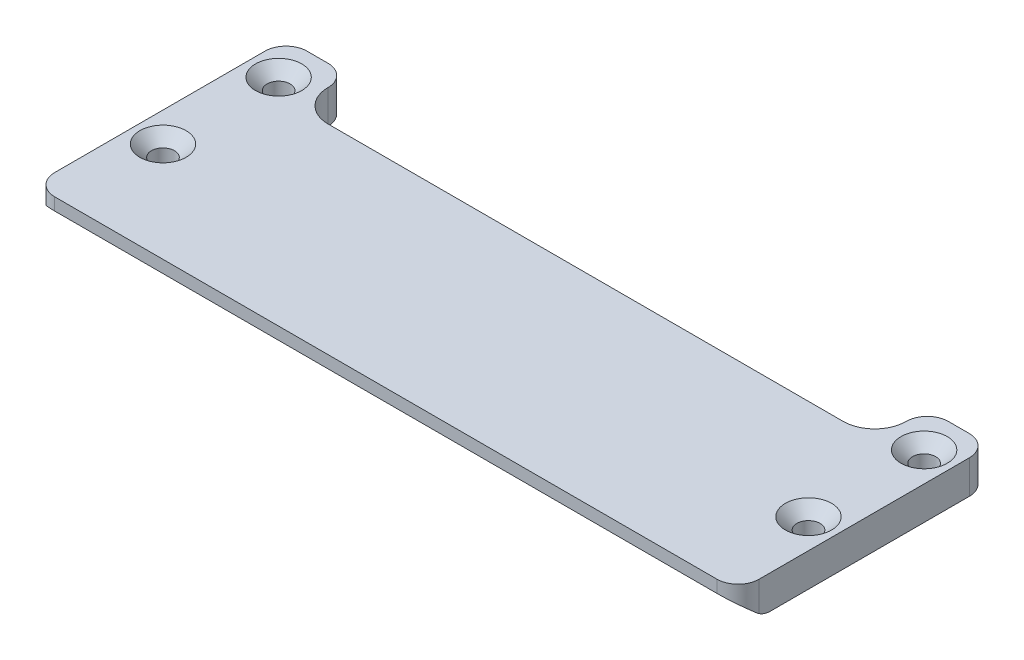
SolidWorks part; units mm, degrees
ref_plane "Front Plane" through (0, 0, 0) normal (0, 0, 1) x (1, 0, 0)
ref_plane "Top Plane" through (0, 0, 0) normal (0, 1, 0) x (1, 0, 0)
ref_plane "Right Plane" through (0, 0, 0) normal (1, 0, 0) x (0, 0, -1)
sketch "Sketch1" plane through (0, 0, 0) normal (0, 1, 0) x (1, 0, 0)
  line L1 (-33.5, -12) -> (33.5, -12)
  line L2 (-33.5, -12) -> (-33.5, 12)
  line L3 (-33.5, 12) -> (33.5, 12)
  line L4 (33.5, -12) -> (33.5, 12)
  line L5 (-33.5, -12) -> (33.5, 12) construction
  line L6 (-33.5, 12) -> (33.5, -12) construction
  point P0 (0, 0)
  dimension "D1" = 67
  dimension "D2" = 24
extrude "Boss-Extrude1" add sketch "Sketch1" along normal blind 3.175
hole_wizard "CSK for M2 Flat Head Machine Screw1" positions "Sketch2" profile "Sketch3" countersink size "M2" standard "ANSI Metric" end condition through all
sketch "Sketch2" plane through (0, 3.175, 0) normal (0, 1, 0) x (1, 0, 0)
  line L1 (-30.7, 8.5) -> (30.7, 8.5) construction
  line L2 (-30.7, 8.5) -> (-30.7, -2.5) construction
  line L4 (30.7, 8.5) -> (30.7, -2.5) construction
  line L6 (0, 0) -> (0, 8.5) construction
  line L7 (33.5, -12) -> (33.5, 12) construction
  line L8 (33.5, 12) -> (-33.5, 12) construction
  point P0 (-30.7, 8.5)
  point P2 (-30.7, -2.5)
  point P4 (30.7, -2.5)
  point P6 (30.7, 8.5)
  dimension "D1" = 2.8
  dimension "D2" = 3.5
  dimension "D3" = 11
sketch "Sketch3" plane through (-30.7, 3.175, -8.5) normal (1, 0, 0) x (0, 0, 1)
  line L0 (0, 0) -> (0, 3.175)
  line L1 (0, 3.175) -> (1.1, 3.175)
  line L2 (1.1, 3.175) -> (1.1, 1.1)
  line L3 (1.1, 1.1) -> (2.2, 0)
  line L5 (2.2, 0) -> (0, 0)
  line L6 (-1.1, 1.1) -> (-2.2, 0) construction
  line L11 (0, -6.35) -> (0, 107.95) construction
  dimension "Thru Hole Dia." = 2.2
  dimension "Thru Hole Depth" = 3.175
  dimension "Near C'Sink Dia." = 4.4
  dimension "Near C'Sink Angle" = 90
chamfer "Chamfer1" distance 2 angle 50 1 edges at (0, 0, 12) first distance on face at (0, 1.5875, 12)
sketch "Sketch4" plane through (0, 3.175, 0) normal (0, 1, 0) x (1, 0, 0)
  line L0 (33.5, 12) -> (-33.5, 12) construction
  line L1 (-27.5, 7) -> (27.5, 7)
  line L2 (-27.5, 7) -> (-27.5, 17)
  line L3 (-27.5, 17) -> (27.5, 17)
  line L4 (27.5, 7) -> (27.5, 17)
  line L5 (-27.5, 7) -> (27.5, 17) construction
  line L6 (-27.5, 17) -> (27.5, 7) construction
  line L7 (33.5, -12) -> (33.5, 12) construction
  point P0 (0, 12)
  dimension "D1" = 6
  dimension "D2" = 10
extrude "Cut-Extrude1" cut sketch "Sketch4" against normal through all
fillet "Fillet2" radius 2 1 edges at (0, 0, 9.6165)
fillet "Fillet4" radius 3 2 edges at (27.5, 1.5875, -7) (-27.5, 1.5875, -7)
fillet "Fillet5" radius 2 6 edges at (33.5, 1.5875, -12) (33.5, 2.5875, 12) (-33.5, 2.5875, 12) (-27.5, 1.5875, -12) (27.5, 1.5875, -12) (-33.5, 1.5875, -12)
